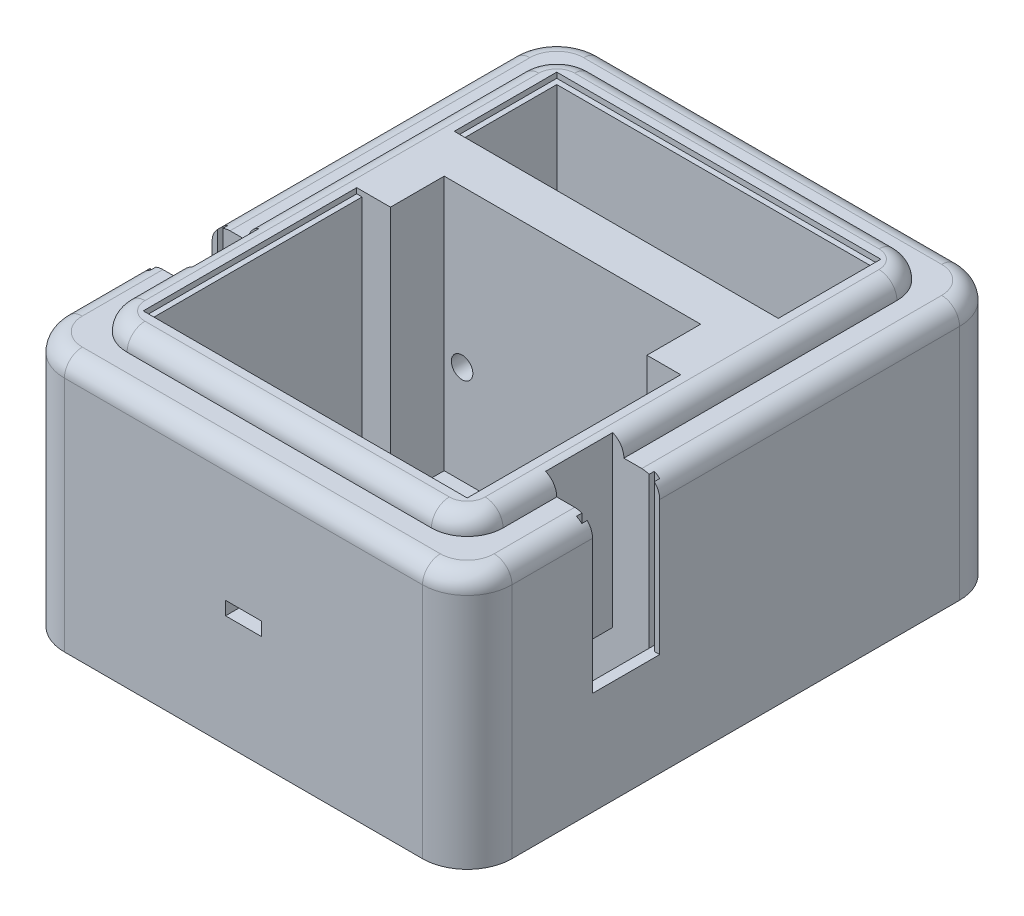
SolidWorks part; units mm, degrees
note: The reader was unsure of these and kept them because the rebuilt part matched: shared geometry of "Skica47<3>".
ref_plane "Přední rovina" through (0, 0, 0) normal (0, 0, 1) x (1, 0, 0)
ref_plane "Horní rovina" through (0, 0, 0) normal (0, 1, 0) x (1, 0, 0)
ref_plane "Pravá rovina" through (0, 0, 0) normal (1, 0, 0) x (0, 0, -1)
sketch "Skica2" plane through (0, 0, 0) normal (0, 1, 0) x (1, 0, 0)
  line L1 (0, 0) -> (100, 0)
  line L2 (0, 0) -> (0, 120)
  line L3 (0, 120) -> (100, 120)
  line L4 (100, 0) -> (100, 120)
  dimension "D1" = 120
  dimension "D2" = 100
extrude "Přidat vysunutím1" add sketch "Skica2" along normal blind 4
sketch "Skica3" plane through (0, 4, 0) normal (0, 1, 0) x (1, 0, 0)
  line L0 (0, 0) -> (100, 0) construction
  line L1 (0, 120) -> (15, 120)
  line L2 (0, 120) -> (0, 0)
  line L3 (0, 0) -> (15, 0)
  line L4 (15, 120) -> (15, 0)
  line L5 (100, 0) -> (100, 120) construction
  line L6 (0, 120) -> (100, 120)
  line L7 (0, 120) -> (0, 105)
  line L8 (0, 105) -> (100, 105)
  line L9 (100, 120) -> (100, 105)
  line L11 (100, 120) -> (85, 120)
  line L12 (100, 120) -> (100, 0)
  line L13 (100, 0) -> (85, 0)
  line L14 (85, 120) -> (85, 0)
  line L15 (100, 0) -> (0, 0)
  line L16 (100, 0) -> (100, 15)
  line L17 (100, 15) -> (0, 15)
  line L18 (0, 0) -> (0, 15)
  line L19 (15, 76.5) -> (85, 76.5)
  line L20 (15, 76.5) -> (15, 61.5)
  line L21 (15, 61.5) -> (85, 61.5)
  line L22 (85, 76.5) -> (85, 61.5)
  line L23 (21.35, 61.5) -> (78.65, 61.5)
  line L24 (21.35, 61.5) -> (21.35, 73.5)
  line L25 (21.35, 73.5) -> (78.65, 73.5)
  line L26 (78.65, 61.5) -> (78.65, 73.5)
  line L27 (15, 76.5) -> (85, 76.5)
  line L28 (15, 76.5) -> (15, 84.5)
  line L29 (15, 84.5) -> (85, 84.5)
  line L30 (85, 76.5) -> (85, 84.5)
  line L31 (21.35, 61.5) -> (15, 61.5)
  line L32 (21.35, 61.5) -> (21.35, 76.5)
  line L33 (21.35, 76.5) -> (15, 76.5)
  line L34 (15, 61.5) -> (15, 76.5)
  line L35 (78.65, 61.5) -> (85, 61.5)
  line L36 (78.65, 61.5) -> (78.65, 76.5)
  line L37 (78.65, 76.5) -> (85, 76.5)
  line L38 (85, 61.5) -> (85, 76.5)
  line L39 (78.65, 73.5) -> (21.35, 73.5)
  line L40 (78.65, 73.5) -> (78.65, 76.5)
  line L41 (78.65, 76.5) -> (21.35, 76.5)
  line L42 (21.35, 73.5) -> (21.35, 76.5)
  line M25 (0, 120) -> (0, 0)
  line M26 (0, 0) -> (100, 0)
  line M27 (100, 0) -> (100, 120)
  line M28 (100, 120) -> (0, 120)
  dimension "D1" = 15
  dimension "D2" = 15
  dimension "D3" = 15
  dimension "D4" = 15
  dimension "D5" = 15
  dimension "D6" = 70
  dimension "D7" = 12
  dimension "D8" = 57.3
  dimension "D9" = 6.35
  dimension "D10" = 28.5
  dimension "D11" = 8
  dimension "D12" = 70
extrude "Přidat vysunutím2" add sketch "Skica3" along normal blind 50 contours L8 L4 M25 M28 | L14 L6 L4 L8 | L17 L4 L8 L2 | L14 L8 M28 M27 | L17 L12 L8 L14 | L29 L4 L19 L27 L14 | L4 L17 M25 M26 | L14 L17 L4 M26 | L17 L14 M27 M26 | L24 L32 L19 L4 L21 | L25 L36 L27 L32 | L36 L26 L21 L14 L19
sketch "Skica4" plane through (0, 4, 0) normal (0, 1, 0) x (1, 0, 0)
  line L1 (15, 105) -> (85, 105)
  line L2 (15, 105) -> (15, 84.5)
  line L3 (15, 84.5) -> (85, 84.5)
  line L4 (85, 105) -> (85, 84.5)
extrude "Přidat vysunutím3" add sketch "Skica4" along normal blind 23
sketch "Skica8" plane through (0, 0, -61.5) normal (0, 0, 1) x (1, 0, 0)
  line L0 (78.65, 54) -> (78.65, 4) construction
  line L1 (78.65, 33) -> (85, 33)
  line L2 (78.65, 33) -> (78.65, 27)
  line L3 (78.65, 27) -> (85, 27)
  line L4 (85, 33) -> (85, 27)
  line L5 (85, 54) -> (85, 4) construction
  line L6 (78.65, 54) -> (85, 54) construction
  dimension "D1" = 6
  dimension "D2" = 21
extrude "Odebrat vysunutím1" cut sketch "Skica8" against normal blind 23
sketch "Skica9" plane through (0, 27, 0) normal (0, 1, 0) x (1, 0, 0)
  line L1 (78.65, 61.5) -> (85, 61.5)
  line L2 (78.65, 61.5) -> (78.65, 63.5)
  line L3 (78.65, 63.5) -> (85, 63.5)
  line L4 (85, 61.5) -> (85, 63.5)
  line L5 (85, 61.5) -> (85, 105) construction
  dimension "D1" = 2
  dimension "D2" = 6.35
extrude "Přidat vysunutím5" add sketch "Skica9" along normal blind 6
sketch "Skica10" plane through (0, 0, -73.5) normal (0, 0, 1) x (1, 0, 0)
  line L0 (21.35, 54) -> (78.65, 54) construction
  line L1 (78.65, 27) -> (78.65, 4) construction
  line L2 (21.35, 54) -> (21.35, 4) construction
  circle A0 centre (25.35, 19) radius 2.4
  circle A1 centre (74.65, 19) radius 2.4
  dimension "D1" = 4.8
  dimension "D2" = 4.8
  dimension "D5" = 4
  dimension "D6" = 4
  dimension "D3" = 35
  dimension "D4" = 35
extrude "Odebrat vysunutím2" cut sketch "Skica10" against normal blind 8
sketch "Skica11" plane through (0, 0, -15) normal (0, 0, -1) x (-1, 0, 0)
  line L0 (-85, 4) -> (-15, 4) construction
  line L1 (-58.3, 30.8) -> (-41.7, 30.8)
  line L2 (-58.3, 30.8) -> (-58.3, 19)
  line L3 (-58.3, 19) -> (-41.7, 19)
  line L4 (-41.7, 30.8) -> (-41.7, 19)
  line L5 (-15, 54) -> (-15, 4) construction
  dimension "D1" = 11.8
  dimension "D2" = 16.6
  dimension "D3" = 15
  dimension "26.7" = 26.7
extrude "Odebrat vysunutím5" cut sketch "Skica11" against normal blind 10
sketch "Skica14" plane through (0, 0, 0) normal (0, 0, 1) x (1, 0, 0)
  line L0 (0, 0) -> (100, 0) construction
  line L1 (46, 28) -> (54, 28)
  line L2 (46, 28) -> (46, 25)
  line L3 (46, 25) -> (54, 25)
  line L4 (54, 28) -> (54, 25)
  line L5 (0, 54) -> (0, 0) construction
  dimension "D1" = 3
  dimension "D2" = 8
  dimension "D3" = 25
  dimension "D4" = 46
extrude "Odebrat vysunutím6" cut sketch "Skica14" against normal blind 5
sketch "Skica15" plane through (0, 54, 0) normal (0, 1, 0) x (1, 0, 0)
  line L0 (0, 0) -> (100, 0) construction
  line L1 (0, 120) -> (8, 120)
  line L2 (0, 120) -> (0, 0)
  line L3 (0, 0) -> (8, 0)
  line L4 (8, 120) -> (8, 0)
  line L5 (100, 120) -> (0, 120) construction
  line L6 (100, 0) -> (0, 0)
  line L7 (100, 0) -> (100, 8)
  line L8 (100, 8) -> (0, 8)
  line L9 (0, 0) -> (0, 8)
  line L10 (100, 0) -> (92, 0)
  line L11 (100, 0) -> (100, 120)
  line L12 (100, 120) -> (92, 120)
  line L13 (92, 0) -> (92, 120)
  line L15 (0, 120) -> (100, 120)
  line L16 (0, 120) -> (0, 112)
  line L17 (0, 112) -> (100, 112)
  line L18 (100, 120) -> (100, 112)
  dimension "D1" = 8
  dimension "D2" = 8
  dimension "D3" = 8
  dimension "D4" = 8
extrude "Odebrat vysunutím7" cut sketch "Skica15" against normal blind 4
sketch "Skica20" plane through (0, 0, 0) normal (-1, 0, 0) x (0, 0, 1)
  line L0 (-112, 54) -> (-8, 54) construction
  line L1 (-43, 54) -> (-28, 54)
  line L2 (-43, 54) -> (-43, 23)
  line L3 (-43, 23) -> (-28, 23)
  line L4 (-28, 54) -> (-28, 23)
  line L6 (-8, 50) -> (-8, 54) construction
  dimension "D1" = 31
  dimension "D2" = 15
  dimension "D3" = 20
extrude "Odebrat vysunutím8" cut sketch "Skica20" against normal blind 10
sketch "Skica21" plane through (100, 0, 0) normal (1, 0, 0) x (0, 0, -1)
  line L0 (8, 54) -> (112, 54) construction
  line L1 (28, 54) -> (43, 54)
  line L2 (28, 54) -> (28, 23)
  line L3 (28, 23) -> (43, 23)
  line L4 (43, 54) -> (43, 23)
  line L5 (8, 50) -> (8, 54) construction
  dimension "D1" = 31
  dimension "D2" = 15
  dimension "D3" = 20
extrude "Odebrat vysunutím10" cut sketch "Skica21" against normal blind 10
sketch "Skica22" plane through (10, 0, 0) normal (-1, 0, 0) x (0, 0, 1)
  line L0 (-43, 54) -> (-43, 23) construction
  line L1 (-43, 23) -> (-28, 23) construction
  circle A0 centre (-35.5, 31.3) radius 2.2
  dimension "D1" = 4.4
  dimension "D2" = 7.5
  dimension "D3" = 8.3
extrude "Odebrat vysunutím11" cut sketch "Skica22" against normal blind 3
sketch "Skica23" plane through (90, 0, 0) normal (1, 0, 0) x (0, 0, -1)
  line L0 (28, 50) -> (28, 23) construction
  line L1 (28, 23) -> (43, 23) construction
  circle A0 centre (35.5, 31.3) radius 2.2
  dimension "D1" = 4.4
  dimension "D2" = 7.5
  dimension "D3" = 8.3
extrude "Odebrat vysunutím12" cut sketch "Skica23" against normal blind 3
sketch "Skica24" plane through (0, 50, 0) normal (0, 1, 0) x (1, 0, 0)
  line L0 (10, 28) -> (0, 28) construction
  line L1 (1.2, 28) -> (2.4, 28)
  line L2 (1.2, 28) -> (1.2, 26.8)
  line L3 (1.2, 26.8) -> (2.4, 26.8)
  line L4 (2.4, 28) -> (2.4, 26.8)
  line L5 (0, 28) -> (0, 0) construction
  line L6 (10, 43) -> (0, 43) construction
  line L7 (1.2, 43) -> (2.4, 43)
  line L8 (1.2, 43) -> (1.2, 44.2)
  line L9 (1.2, 44.2) -> (2.4, 44.2)
  line L10 (2.4, 43) -> (2.4, 44.2)
  line L11 (0, 120) -> (0, 43) construction
  line L12 (92, 28) -> (100, 28) construction
  line L13 (97.6, 28) -> (98.8, 28)
  line L14 (97.6, 28) -> (97.6, 26.8)
  line L15 (97.6, 26.8) -> (98.8, 26.8)
  line L16 (98.8, 28) -> (98.8, 26.8)
  line L17 (100, 43) -> (92, 43) construction
  line L18 (97.6, 43) -> (98.8, 43)
  line L19 (97.6, 43) -> (97.6, 44.2)
  line L20 (97.6, 44.2) -> (98.8, 44.2)
  line L21 (98.8, 43) -> (98.8, 44.2)
  line L22 (100, 0) -> (100, 28) construction
  line L23 (100, 43) -> (100, 120) construction
  dimension "D1" = 1.2
  dimension "D2" = 1.2
  dimension "D3" = 1.2
  dimension "D4" = 1.2
  dimension "D5" = 1.2
  dimension "D6" = 1.2
  dimension "D7" = 1.2
  dimension "D8" = 1.2
  dimension "D9" = 1.2
extrude "Odebrat vysunutím14" cut sketch "Skica24" against normal blind 27
sketch "Skica26" plane through (0, 23, 0) normal (0, 1, 0) x (1, 0, 0)
  line L0 (15, 61.5) -> (15, 15) construction
  line L1 (2.4, 43) -> (15, 43)
  line L2 (2.4, 43) -> (2.4, 28)
  line L3 (2.4, 28) -> (15, 28)
  line L4 (15, 43) -> (15, 28)
  line L5 (85, 61.5) -> (85, 15) construction
  line L6 (97.6, 43) -> (85, 43)
  line L7 (97.6, 43) -> (97.6, 28)
  line L8 (97.6, 28) -> (85, 28)
  line L9 (85, 43) -> (85, 28)
  line L10 (85, 15) -> (15, 15) construction
  line L12 (85, 15) -> (15, 15) construction
  dimension "D1" = 13
  dimension "D2" = 13
extrude "Odebrat vysunutím16" cut sketch "Skica26" against normal blind 19
sketch "Skica32" plane through (13, 0, 0) normal (-1, 0, 0) x (0, 0, 1)
  circle A0 centre (-35.5, 31.3) radius 2.2
extrude "Odebrat vysunutím19" cut sketch "Skica32" against normal through all
sketch "Skica33" plane through (78.65, 0, 0) normal (-1, 0, 0) x (0, 0, 1)
  line L0 (-61.5, 54) -> (-61.5, 4) construction
  line L1 (-63.5, 33) -> (-61.5, 33)
  line L2 (-63.5, 33) -> (-63.5, 27)
  line L3 (-63.5, 27) -> (-61.5, 27)
  line L4 (-61.5, 33) -> (-61.5, 27)
extrude "Odebrat vysunutím20" cut sketch "Skica33" against normal up to surface (6.35 mm away) up to face at (85, 31.3, -37.7)
sketch "Skica35" plane through (0, 19, 0) normal (0, 1, 0) x (1, 0, 0)
  line L1 (41.7, 15) -> (58.3, 15)
  line L2 (41.7, 15) -> (41.7, 5)
  line L3 (41.7, 5) -> (58.3, 5)
  line L4 (58.3, 15) -> (58.3, 5)
extrude "Odebrat vysunutím21" cut sketch "Skica35" against normal blind 1.5
sketch "Skica38" plane through (0, 27, 0) normal (0, 1, 0) x (1, 0, 0)
  line L1 (78.65, 61.5) -> (79.65, 61.5)
  line L2 (78.65, 61.5) -> (78.65, 84.5)
  line L3 (78.65, 84.5) -> (79.65, 84.5)
  line L4 (79.65, 61.5) -> (79.65, 84.5)
  dimension "D1" = 1
extrude "Přidat vysunutím9" add sketch "Skica38" along normal blind 15
sketch "Skica39" plane through (0, 0, -61.5) normal (0, 0, 1) x (1, 0, 0)
  line L1 (79.65, 33) -> (85, 33)
  line L2 (79.65, 33) -> (79.65, 38)
  line L3 (79.65, 38) -> (85, 38)
  line L4 (85, 33) -> (85, 38)
  line L5 (85, 54) -> (85, 33) construction
  dimension "D1" = 5
  dimension "D2" = 5.35
extrude "Odebrat vysunutím23" cut sketch "Skica39" against normal up to surface (23 mm away) up to face at (59.8833, 38, -84.5)
sketch "Skica40" plane through (10, 0, 0) normal (-1, 0, 0) x (0, 0, 1)
  line L1 (-43, 54) -> (-28, 54)
  line L2 (-43, 54) -> (-43, 23)
  line L3 (-43, 23) -> (-28, 23)
  line L4 (-28, 54) -> (-28, 23)
extrude "Odebrat vysunutím24" cut sketch "Skica40" against normal blind 0.5
sketch "Skica41" plane through (90, 0, 0) normal (1, 0, 0) x (0, 0, -1)
  line L1 (28, 23) -> (43, 23)
  line L2 (28, 23) -> (28, 54)
  line L3 (28, 54) -> (43, 54)
  line L4 (43, 23) -> (43, 54)
extrude "Odebrat vysunutím25" cut sketch "Skica41" against normal blind 0.5
sketch "Skica43" plane through (0, 54, 0) normal (0, 1, 0) x (1, 0, 0)
  line L0 (92, 8) -> (8, 8) construction
  line L1 (8, 112) -> (85, 112)
  line L2 (8, 112) -> (8, 105)
  line L3 (8, 105) -> (85, 105)
  line L4 (85, 112) -> (85, 105)
  line L5 (85, 8) -> (92, 8)
  line L6 (85, 8) -> (85, 112)
  line L7 (85, 112) -> (92, 112)
  line L8 (92, 8) -> (92, 112)
  line L9 (15, 84.5) -> (85, 84.5) construction
  line L10 (8, 105) -> (15, 105)
  line L11 (8, 105) -> (8, 15)
  line L12 (8, 15) -> (15, 15)
  line L13 (15, 105) -> (15, 15)
  line L14 (8, 15) -> (85, 15)
  line L15 (8, 15) -> (8, 8)
  line L16 (8, 8) -> (85, 8)
  line L17 (85, 15) -> (85, 8)
  line L18 (78.65, 61.5) -> (85, 61.5)
  line L19 (78.65, 61.5) -> (78.65, 84.5)
  line L20 (78.65, 84.5) -> (85, 84.5)
  line L21 (85, 61.5) -> (85, 84.5)
  line L23 (15, 61.5) -> (21.35, 61.5)
  line L24 (15, 61.5) -> (15, 73.5)
  line L25 (15, 73.5) -> (21.35, 73.5)
  line L26 (21.35, 61.5) -> (21.35, 73.5)
  line L27 (78.65, 84.5) -> (15, 84.5)
  line L28 (78.65, 84.5) -> (78.65, 73.5)
  line L29 (78.65, 73.5) -> (15, 73.5)
  line L30 (15, 84.5) -> (15, 73.5)
extrude "Přidat vysunutím10" add sketch "Skica43" along normal blind 7 contours L4 L5 L3 L24 | L13 L23 L3 L5 L6 L7 L8 L9 L12 L15 | L19 L12 L6 L21 | L6 L10 L11 L0 L1 L2 L3 L4 L20 L13 | L13 L25 L18 L19 L21 | L25 L13 L16 L17 | L12 L9 L10 L6 L14
sketch "Skica44" plane through (0, 50, 0) normal (0, 1, 0) x (1, 0, 0)
  line L0 (8, 28) -> (8, 8) construction
  line L1 (0, 120) -> (2.4, 120)
  line L2 (0, 120) -> (0, 44.2)
  line L3 (0, 44.2) -> (2.4, 44.2)
  line L4 (2.4, 120) -> (2.4, 44.2)
  line L5 (0, 43) -> (1.2, 43)
  line L6 (0, 43) -> (0, 44.2)
  line L7 (0, 44.2) -> (1.2, 44.2)
  line L8 (1.2, 43) -> (1.2, 44.2)
  line L9 (0, 28) -> (1.2, 28)
  line L10 (0, 28) -> (0, 26.8)
  line L11 (0, 26.8) -> (1.2, 26.8)
  line L12 (1.2, 28) -> (1.2, 26.8)
  line L13 (2.4, 28) -> (8, 28)
  line L14 (2.4, 28) -> (2.4, 26.8)
  line L15 (2.4, 26.8) -> (8, 26.8)
  line L16 (8, 28) -> (8, 26.8)
  line L17 (92, 43) -> (92, 112) construction
  line L18 (8, 8) -> (0, 8)
  line L19 (8, 8) -> (8, 26.8)
  line L20 (8, 26.8) -> (0, 26.8)
  line L21 (0, 8) -> (0, 26.8)
  line L22 (0, 8) -> (100, 8)
  line L23 (0, 8) -> (0, 0)
  line L24 (0, 0) -> (100, 0)
  line L25 (100, 8) -> (100, 0)
  line L26 (92, 28) -> (97.6, 28)
  line L27 (92, 28) -> (92, 26.8)
  line L28 (92, 26.8) -> (97.6, 26.8)
  line L29 (97.6, 28) -> (97.6, 26.8)
  line L30 (100, 28) -> (98.8, 28)
  line L31 (100, 28) -> (100, 26.8)
  line L32 (100, 26.8) -> (98.8, 26.8)
  line L33 (98.8, 28) -> (98.8, 26.8)
  line L34 (92, 26.8) -> (100, 26.8)
  line L35 (92, 26.8) -> (92, 8)
  line L36 (92, 8) -> (100, 8)
  line L37 (100, 26.8) -> (100, 8)
  line L38 (100, 43) -> (98.8, 43)
  line L39 (100, 43) -> (100, 44.2)
  line L40 (100, 44.2) -> (98.8, 44.2)
  line L41 (98.8, 43) -> (98.8, 44.2)
  line L42 (97.6, 43) -> (92, 43)
  line L43 (97.6, 43) -> (97.6, 44.2)
  line L44 (97.6, 44.2) -> (92, 44.2)
  line L45 (92, 43) -> (92, 44.2)
  line L47 (92, 44.2) -> (100, 44.2)
  line L48 (92, 44.2) -> (92, 120)
  line L49 (92, 120) -> (100, 120)
  line L50 (100, 44.2) -> (100, 120)
  line L51 (2.4, 120) -> (92, 120)
  line L52 (2.4, 120) -> (2.4, 112)
  line L53 (2.4, 112) -> (92, 112)
  line L54 (92, 120) -> (92, 112)
  line L55 (8, 43) -> (2.4, 43)
  line L56 (8, 43) -> (8, 112)
  line L57 (8, 112) -> (2.4, 112)
  line L58 (2.4, 43) -> (2.4, 112)
  line M1 (1.2, 43) -> (1.2, 44.2)
  line M3 (2.4, 44.2) -> (2.4, 43)
  line M4 (2.4, 43) -> (8, 43)
  line M5 (8, 43) -> (8, 112)
  line M6 (8, 112) -> (92, 112)
  line M7 (92, 112) -> (92, 43)
  line M8 (92, 43) -> (97.6, 43)
  line M9 (97.6, 43) -> (97.6, 44.2)
  line M10 (97.6, 44.2) -> (98.8, 44.2)
  line M11 (98.8, 44.2) -> (98.8, 43)
  line M12 (98.8, 43) -> (100, 43)
  line M13 (100, 43) -> (100, 120)
  line M14 (100, 120) -> (0, 120)
  line M15 (0, 120) -> (0, 43)
  line M16 (0, 43) -> (1.2, 43)
extrude "Přidat vysunutím11" add sketch "Skica44" along normal blind 7 contours L25 L22 L18 L23 L24 | L48 L44 L40 M7 M10 M13 M14 | L53 L4 M3 M4 M5 | L4 L53 L48 M6 M14 | L29 L26 L27 L28 | L30 L33 L32 L31 | L37 L32 L34 L28 L35 L22 | L40 M13 M11 M12 | L44 M9 M7 M8 | L21 L18 L19 L15 L20 L11 | L12 L9 L10 L11 | L16 L13 L14 L15 | L3 M15 M16 M1
sketch "Skica45" plane through (0, 61, 0) normal (0, 1, 0) x (1, 0, 0)
  line L0 (85, 61.5) -> (85, 105) construction
  line L1 (15, 105) -> (85, 105)
  line L2 (15, 105) -> (15, 106.2)
  line L3 (15, 106.2) -> (85, 106.2)
  line L4 (85, 105) -> (85, 106.2)
  line L6 (15, 84.5) -> (13.8, 84.5)
  line L7 (15, 84.5) -> (15, 106.2)
  line L8 (15, 106.2) -> (13.8, 106.2)
  line L9 (13.8, 84.5) -> (13.8, 106.2)
  line L10 (13.8, 84.5) -> (85, 84.5)
  line L11 (13.8, 84.5) -> (13.8, 83.3)
  line L12 (13.8, 83.3) -> (85, 83.3)
  line L13 (85, 84.5) -> (85, 83.3)
  line L14 (85, 106.2) -> (86.2, 106.2)
  line L15 (85, 106.2) -> (85, 83.3)
  line L16 (85, 83.3) -> (86.2, 83.3)
  line L17 (86.2, 106.2) -> (86.2, 83.3)
  line L18 (15, 15) -> (13.8, 15)
  line L19 (15, 15) -> (15, 61.5)
  line L20 (15, 61.5) -> (13.8, 61.5)
  line L21 (13.8, 15) -> (13.8, 61.5)
  line L22 (85, 15) -> (13.8, 15)
  line L23 (85, 15) -> (85, 13.8)
  line L24 (85, 13.8) -> (13.8, 13.8)
  line L25 (13.8, 15) -> (13.8, 13.8)
  line L26 (85, 61.5) -> (86.2, 61.5)
  line L27 (85, 61.5) -> (85, 13.8)
  line L28 (85, 13.8) -> (86.2, 13.8)
  line L29 (86.2, 61.5) -> (86.2, 13.8)
  dimension "D1" = 1.2
  dimension "D2" = 1.2
  dimension "D3" = 1.2
  dimension "D4" = 71.2
  dimension "D5" = 1.2
  dimension "D6" = 1.2
  dimension "D7" = 71.2
  dimension "D8" = 1.2
  dimension "D9" = 1.2
  dimension "D10" = 0
  dimension "D11" = 46.5
  dimension "D12" = 21.7
extrude "Odebrat vysunutím26" cut sketch "Skica45" against normal blind 1.2 contours L21 L20 L19 L18 | L24 L25 L22 L23 | L27 L28 L29 L26 | L9 L8 L7 L6 | L3 L2 L1 L4 | L10 L13 L12 L11 | L15 L16 L17 L14
fillet "Zaoblit1" radius 10 4 edges at (100, 28.5, 0) (100, 28.5, -120) (0, 28.5, -120) (0, 28.5, 0)
fillet "Zaoblit2" radius 8 4 edges at (8, 59, -8) (8, 59, -112) (92, 59, -112) (92, 59, -8)
fillet "Zaoblit3" radius 4 50 edges at (8, 59, -43) (92, 59, -28) (8, 61, -22) (90.75, 61, -28) (89.5, 61, -35.5) (90.75, 61, -43) (92, 61, -73.5) (9.25, 61, -43) (10.5, 61, -35.5) (9.25, 61, -28) (8, 59, -28) (100, 57, -19) (97.6, 57, -27.4) (1.8, 57, -26.8) (1.2, 57, -27.4) (98.8, 57, -27.4) (98.2, 57, -26.8) (2.4, 57, -27.4) (0, 57, -19) (92, 59, -43) (98.2, 57, -44.2) (97.6, 57, -43.6) (98.8, 57, -43.6) (100, 57, -76.5) (1.2, 57, -43.6) (1.8, 57, -44.2) (2.4, 57, -43.6) (50, 57, 0) (2.9289, 57, -2.9289) (97.0711, 57, -2.9289) (50, 57, -120) (0, 57, -76.5) (2.9289, 57, -117.0711) (97.0711, 57, -117.0711) (8, 59, -16) (50, 61, -8) (92, 61, -22) (50, 61, -112) (8, 61, -73.5) (89.6569, 61, -10.3431) (89.6569, 61, -109.6569) (10.3431, 61, -109.6569) (10.3431, 61, -10.3431) (84, 59, -8) (16, 59, -8) (84, 59, -112) (16, 59, -112) (8, 59, -104) (92, 59, -104) (92, 59, -16)
sketch "Skica47" plane through (0, 0, -73.5) normal (0, 0, 1) x (1, 0, 0)
  line L2 (21.35, 4) -> (78.65, 4) construction
  circle A0 centre (25.35, 19) radius 2.4
  circle A1 centre (74.65, 19) radius 2.4
  circle A2 centre (25.35, 26) radius 2.4
  circle A3 centre (74.65, 26) radius 2.4
  point P10 (0, 0)
  point P13 (0, 0)
  circle M1 centre (25.35, 19) radius 2.4
  circle M2 centre (74.65, 19) radius 2.4
  dimension "D1" = 4.8
  dimension "D2" = 4.8
  dimension "D3" = 4.8
  dimension "D4" = 4.8
  dimension "D5" = 7
  dimension "D7" = 22
  dimension "D6" = 7
  dimension "D8" = 22
extrude "Přidat vysunutím13" add sketch "Skica47" against normal blind 7 contours M1 | M2
extrude "Odebrat vysunutím27" cut sketch "Skica47<3>" against normal blind 7 contours A2 | A3
sketch "Skica47<3>" plane through (0, 0, -73.5) normal (0, 0, 1) x (1, 0, 0) same geometry as "Skica47"
